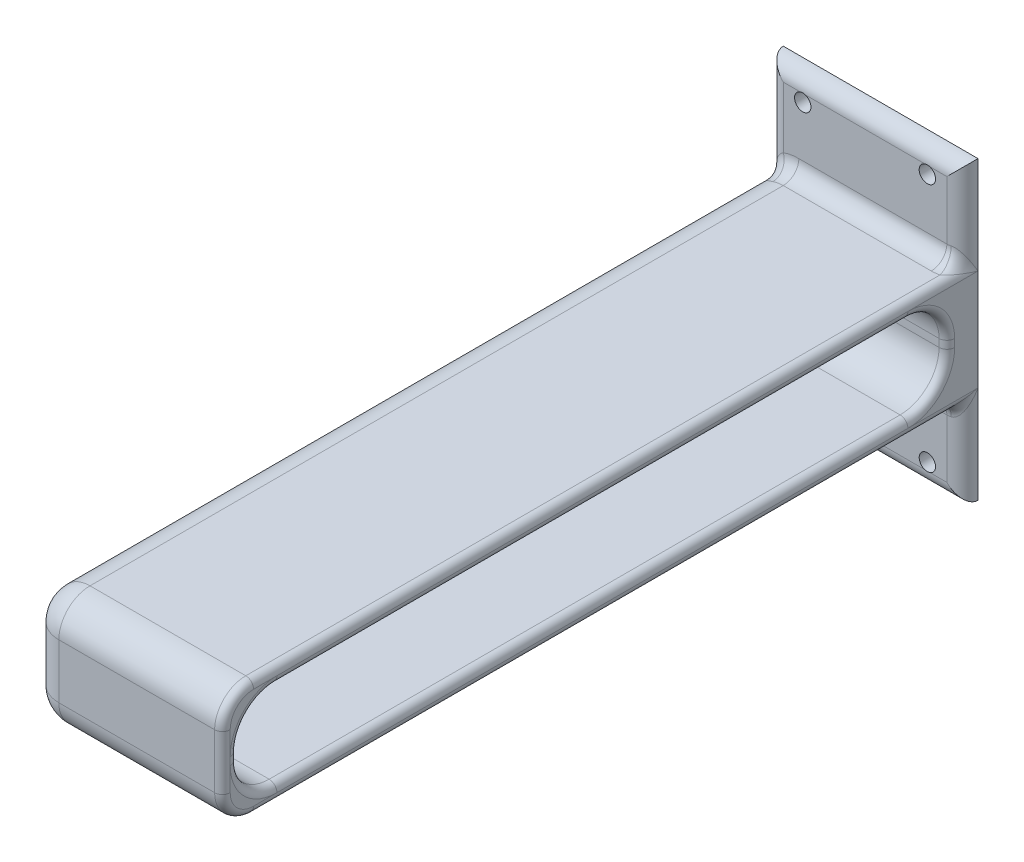
SolidWorks part; units mm, degrees
ref_plane "Plan de face" through (0, 0, 0) normal (0, 0, 1) x (1, 0, 0)
ref_plane "Plan de dessus" through (0, 0, 0) normal (0, 1, 0) x (1, 0, 0)
ref_plane "Plan de droite" through (0, 0, 0) normal (1, 0, 0) x (0, 0, -1)
sketch "Esquisse1" plane through (0, 0, 0) normal (0, 0, 1) x (1, 0, 0)
  line L0 (0, 15) -> (0, 0)
  line L1 (0, 0) -> (25, 0)
  line L3 (0, 15) -> (25, 15)
  line L4 (25, 0) -> (25, 15)
  dimension "D1" = 25
  dimension "D2" = 15
extrude "Boss.-Extru.1" add sketch "Esquisse1" along normal blind 95
shell "Coque1" thickness 2 removed face at (25, 7.5, 47.5)
fillet "Congé1" radius 4 5 edges at (0, 15, 47.5) (0, 0, 47.5) (0, 7.5, 95) (12.5, 15, 95) (12.5, 0, 95)
fillet "Congé2" radius 5 7 edges at (2, 7.5, 93) (2, 2, 47.5) (2, 13, 47.5) (13.5, 13, 93) (13.5, 2, 93) (13.5, 13, 2) (13.5, 2, 2)
fillet "Congé3" radius 1 13 edges at (25, 13, 47.5) (25, 11.5355, 91.5355) (25, 7.5, 93) (25, 3.4645, 91.5355) (25, 15, 45.5) (25, 13.8284, 93.8284) (25, 7.5, 95) (25, 1.1716, 93.8284) (25, 7.5, 2) (25, 2, 47.5) (25, 0, 45.5) (25, 11.5355, 3.4645) (25, 3.4645, 3.4645)
sketch "Esquisse2" plane through (0, 0, 0) normal (0, 0, -1) x (-1, 0, 0)
  line L0 (-4, 0) -> (-24, 0) construction
  line L1 (-25, 26.5) -> (0, 26.5)
  line L2 (-25, 26.5) -> (-25, -11.5)
  line L3 (-25, -11.5) -> (0, -11.5)
  line L4 (0, 26.5) -> (0, -11.5)
  dimension "D1" = 38
  dimension "D2" = 11.5
extrude "Boss.-Extru.2" add sketch "Esquisse2" along normal blind 2
fillet "Congé4" radius 2 6 edges at (12.5, -11.5, 0) (12.5, 26.5, 0) (0, 18.75, 0) (0, -3.75, 0) (25, 20.25, 0) (25, -5.25, 0)
sketch "Esquisse3" plane through (0, 0, -2) normal (0, 0, -1) x (-1, 0, 0)
  line L0 (-4.5, -8.5) -> (-20.5, -8.5) construction
  line L1 (-20.5, -8.5) -> (-20.5, 23.5) construction
  line L2 (-20.5, 23.5) -> (-4.5, 23.5) construction
  line L3 (-4.5, 23.5) -> (-4.5, -8.5) construction
  line L4 (-25, -11.5) -> (0, -11.5) construction
  line L5 (0, 26.5) -> (-25, 26.5) construction
  line L6 (-25, 26.5) -> (-25, 14) construction
  line L7 (0, 11) -> (0, 26.5) construction
  circle A0 centre (-20.5, 23.5) radius 1.05
  circle A1 centre (-20.5, -8.5) radius 1.05
  circle A2 centre (-4.5, -8.5) radius 1.05
  circle A3 centre (-4.5, 23.5) radius 1.05
  dimension "D5" = 2.1
  dimension "D6" = 2.1
  dimension "D7" = 2.1
  dimension "D8" = 2.1
  dimension "D1" = 3
  dimension "D2" = 3
  dimension "D3" = 4.5
  dimension "D4" = 4.5
extrude "Enlèv. mat.-Extru.1" cut sketch "Esquisse3" against normal through all
fillet "Congé5" radius 2 10 edges at (0.52, 2.0278, -0.6548) (2.9647, 0.1363, 0) (24.74, 0.3274, -1.0139) (23.5176, 0, -0.0681) (24.74, 14.6726, -1.0139) (23.5176, 15, -0.0681) (0.52, 12.9722, -0.6548) (2.9647, 14.8637, 0) (13.5, 0, 0) (13.5, 15, 0)
